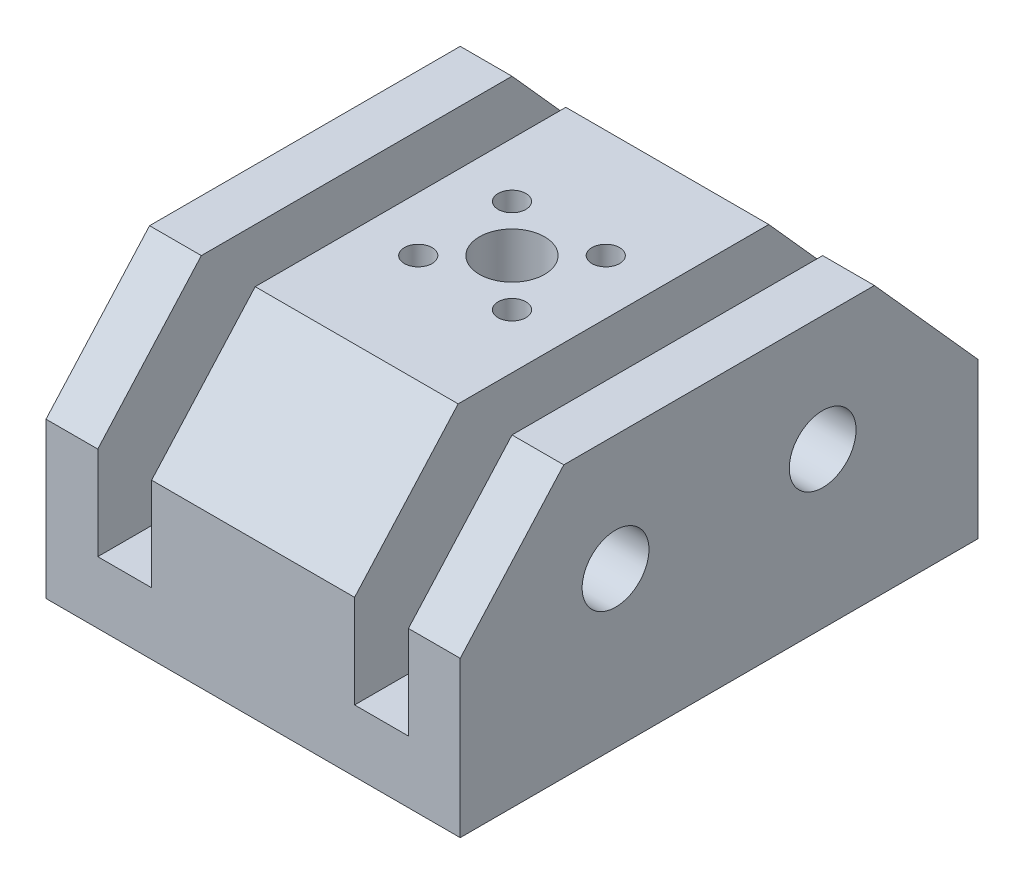
SolidWorks part; units mm, degrees
ref_plane "Front Plane" through (0, 0, 0) normal (0, 0, 1) x (1, 0, 0)
ref_plane "Top Plane" through (0, 0, 0) normal (0, 1, 0) x (1, 0, 0)
ref_plane "Right Plane" through (0, 0, 0) normal (1, 0, 0) x (0, 0, -1)
sketch "Sketch1" plane through (0, 0, 0) normal (1, 0, 0) x (0, 0, -1)
  line L1 (0, 0) -> (63.5, 0)
  line L2 (0, 0) -> (0, 6.35)
  line L3 (0, 6.35) -> (63.5, 6.35)
  line L4 (63.5, 0) -> (63.5, 6.35)
  dimension "D1" = 6.35
  dimension "D2" = 63.5
extrude "Boss-Extrude1" add sketch "Sketch1" against normal blind 50.8
sketch "Sketch2" plane through (0, 0, 0) normal (1, 0, 0) x (0, 0, -1)
  line L0 (0, 6.35) -> (0, 19.05)
  line L1 (0, 19.05) -> (12.7, 33.249)
  line L2 (12.7, 33.249) -> (50.8, 33.249)
  line L3 (50.8, 33.249) -> (63.5, 19.05)
  line L4 (63.5, 19.05) -> (63.5, 6.35)
  line L5 (63.5, 6.35) -> (0, 6.35)
  point P7 (31.75, 33.249)
  point P10 (31.75, 6.35)
  dimension "D1" = 38.1
  dimension "D2" = 12.7
  dimension "D3" = 12.7
  dimension "D4" = 19.05
  dimension "D5" = 19.05
extrude "Boss-Extrude2" add sketch "Sketch2" against normal blind 50.8
sketch "Sketch10" plane through (0, 0, -63.5) normal (0, 0, -1) x (-1, 0, 0)
  line L1 (50.8, 33.249) -> (0, 33.249) construction
  line L3 (6.35, 7.62) -> (6.35, 33.249)
  line L4 (6.35, 33.249) -> (12.954, 33.249)
  line L5 (12.954, 7.62) -> (12.954, 33.249)
  line L6 (6.35, 7.62) -> (12.954, 7.62)
  line L8 (50.8, 0) -> (0, 0) construction
  point P11 (12.954, 7.62)
  dimension "D1" = 7.62
  dimension "D2" = 6.604
  dimension "D3" = 6.35
extrude "Cut-Extrude1" cut sketch "Sketch10" against normal through all
pattern_linear "LPattern3" count 2 spacing 31.496 along (-1, 0, 0) of "Cut-Extrude1"
sketch "Sketch11" plane through (0, 0, 0) normal (1, 0, 0) x (0, 0, -1)
  circle A0 centre (19.05, 19.05) radius 4.0957
  circle A1 centre (19.05, 19.05) radius 7.9375 construction
  circle A2 centre (44.45, 19.05) radius 4.0958
  circle A3 centre (44.45, 19.05) radius 7.9375 construction
  dimension "D1" = 8.1915
  dimension "D3" = 15.875
  dimension "D4" = 8.1915
  dimension "D6" = 15.875
  dimension "D2" = 6.35
  dimension "D5" = 6.35
extrude "Cut-Extrude2" cut sketch "Sketch11" against normal through all
sketch "Sketch14" plane through (0, 33.249, 0) normal (0, 1, 0) x (1, 0, 0)
  line L3 (-37.846, 12.7) -> (-37.846, 50.8) construction
  point P0 (-25.4, 31.75)
  point P4 (-37.846, 31.75)
  dimension "D1" = 12.446
sketch "Sketch17" plane through (0, 40.0201, -44.7438) normal (0, 0.6667, -0.7454) x (-1, 0, 0)
  line L0 (12.954, -28.1343) -> (12.954, -9.0843) construction
  line L1 (37.846, -9.0843) -> (12.954, -9.0843) construction
  point P0 (25.4, -18.6093)
  point P4 (12.954, -18.6093)
  point P7 (25.4, -9.0843)
sketch "Sketch18" plane through (0, 8.4667, 9.466) normal (0, 0.6667, 0.7454) x (1, 0, 0)
  line L0 (-12.954, 33.249) -> (-12.954, 14.199) construction
  line L1 (-37.846, 33.249) -> (-12.954, 33.249) construction
  point P0 (-25.4, 23.724)
  point P1 (-25.4, 23.724)
  point P4 (-12.954, 23.724)
  point P7 (-25.4, 33.249)
ref_plane "Plane2" through (0, 33.02, 0) normal (0, -1, 0) x (-1, 0, 0)
fillet "Fillet1" [suppressed] radius 2.54
sketch "Sketch21" plane through (0, 0, 0) normal (0, -1, 0) x (1, 0, 0)
  line L0 (-25.4, -63.5) -> (-25.4, 0) construction
  line L1 (-50.8, -63.5) -> (0, -63.5) construction
  line L2 (-50.8, 0) -> (0, 0) construction
  line L3 (-50.8, -31.75) -> (0, -31.75) construction
  line L4 (-50.8, 0) -> (-50.8, -63.5) construction
  line L5 (0, 0) -> (0, -63.5) construction
  circle A0 centre (-31.15, -37.5) radius 1.7
  circle A1 centre (-31.15, -26) radius 1.7
  circle A2 centre (-19.65, -26) radius 1.7
  circle A3 centre (-19.65, -37.5) radius 1.7
  point P14 (-25.4, -31.75)
  point P24 (-25.4, -31.75)
  dimension "D1" = 3.4
  dimension "D3" = 5.75
  dimension "D2" = 5.75
  dimension "D4" = 4
sketch "Sketch22" plane through (0, 0, 0) normal (0, -1, 0) x (1, 0, 0)
  line L1 (-25.4, -63.5) -> (-25.4, 0) construction
  line L2 (-50.8, -63.5) -> (0, -63.5) construction
  line L3 (-50.8, 0) -> (0, 0) construction
  line L4 (0, -31.75) -> (-50.8, -31.75) construction
  line L6 (0, 0) -> (0, -63.5) construction
  line L7 (-50.8, 0) -> (-50.8, -63.5) construction
  circle A1 centre (-25.4, -31.75) radius 11
  dimension "D1" = 22
extrude "Cut-Extrude7" cut sketch "Sketch21" against normal up to next
extrude "Cut-Extrude8" cut sketch "Sketch22" against normal blind 3
sketch "Sketch24" plane through (0, 0, 0) normal (0, -1, 0) x (1, 0, 0)
  line L0 (-25.4, -63.5) -> (-25.4, 0) construction
  line L1 (-50.8, -63.5) -> (0, -63.5) construction
  line L2 (-50.8, 0) -> (0, 0) construction
  line L3 (0, -31.75) -> (-50.8, -31.75) construction
  line L4 (0, 0) -> (0, -63.5) construction
  line L5 (-50.8, 0) -> (-50.8, -63.5) construction
  circle A0 centre (-25.4, -31.75) radius 4
extrude "Cut-Extrude10" cut sketch "Sketch24" against normal through all
